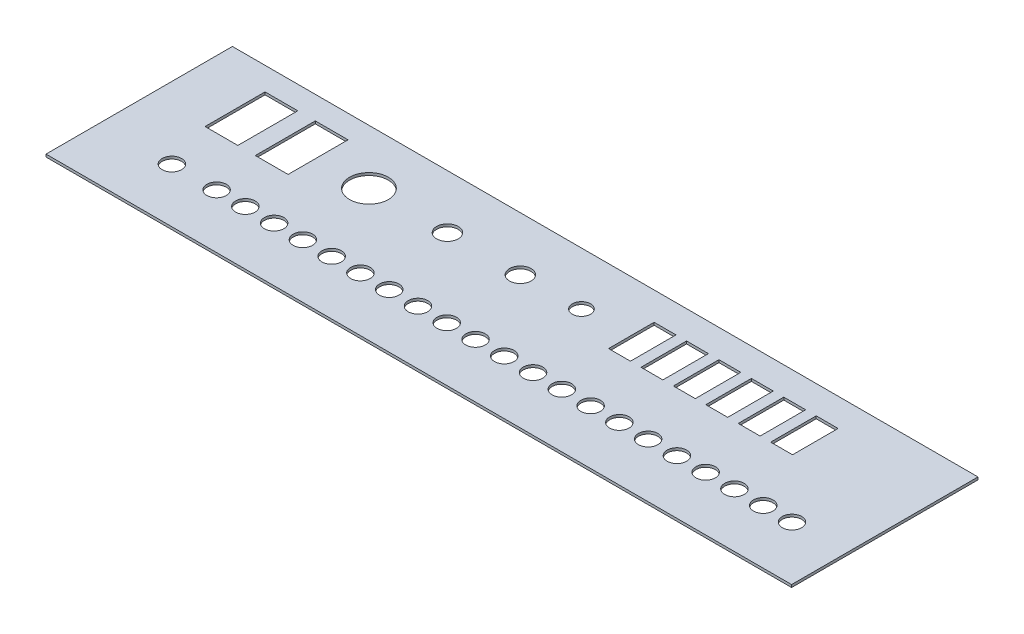
SolidWorks part; units mm, degrees
ref_plane "Front Plane" through (0, 0, 0) normal (0, 0, 1) x (1, 0, 0)
ref_plane "Top Plane" through (0, 0, 0) normal (0, 1, 0) x (1, 0, 0)
ref_plane "Right Plane" through (0, 0, 0) normal (1, 0, 0) x (0, 0, -1)
sketch "Boceto" plane through (0, 0, 0) normal (0, 1, 0) x (1, 0, 0)
  line L0 (-59.1, 30.6902) -> (-173.0029, 30.6902) construction
  line L5 (-59.1, -51.6098) -> (395.9, -51.6098) construction
  line L6 (-59.1, -51.6098) -> (-59.1, 63.3902) construction
  line L7 (-59.1, 63.3902) -> (395.9, 63.3902) construction
  line L8 (395.9, -51.6098) -> (395.9, 63.3902) construction
  line L9 (-28.6, 48.9902) -> (-8.6, 48.9902) construction
  line L10 (-28.6, 48.9902) -> (-28.6, 12.3902) construction
  line L11 (-28.6, 12.3902) -> (-8.6, 12.3902) construction
  line L12 (-8.6, 48.9902) -> (-8.6, 12.3902) construction
  line L13 (-28.6, 48.9902) -> (-8.6, 12.3902) construction
  line L14 (-28.6, 12.3902) -> (-8.6, 48.9902) construction
  line L15 (-59.1, -18.1098) -> (395.9, -18.1098) construction
  line L16 (2.4, 12.3902) -> (22.4, 12.3902) construction
  line L17 (2.4, 12.3902) -> (2.4, 48.9902) construction
  line L18 (2.4, 48.9902) -> (22.4, 48.9902) construction
  line L19 (22.4, 12.3902) -> (22.4, 48.9902) construction
  line L20 (2.4, 12.3902) -> (22.4, 48.9902) construction
  line L21 (2.4, 48.9902) -> (22.4, 12.3902) construction
  line L22 (174.9, 49.7902) -> (194.9, 49.7902) construction
  line L23 (174.9, 49.7902) -> (174.9, 11.7902) construction
  line L24 (174.9, 11.7902) -> (194.9, 11.7902) construction
  line L25 (194.9, 49.7902) -> (194.9, 11.7902) construction
  line L26 (174.9, 49.7902) -> (194.9, 11.7902) construction
  line L27 (174.9, 11.7902) -> (194.9, 49.7902) construction
  line L34 (211.4, 17.5561) -> (331, 17.5561) construction
  line L35 (211.4, 17.5561) -> (211.4, 46.5902) construction
  line L36 (211.4, 46.5902) -> (331, 46.5902) construction
  line L37 (331, 17.5561) -> (331, 46.5902) construction
  line L38 (211.4, 17.5561) -> (331, 46.5902) construction
  line L39 (211.4, 46.5902) -> (331, 17.5561) construction
  circle A0 centre (54.9, 29.6902) radius 11.1 construction
  circle A1 centre (102.75, 30.2402) radius 4.85 construction
  circle A2 centre (147.75, 30.2402) radius 4.85 construction
  circle A3 centre (-18.9, -18.1098) radius 6 construction
  circle A4 centre (8.7, -18.1098) radius 6 construction
  circle A5 centre (26.45, -18.1098) radius 6 construction
  circle A6 centre (44.2, -18.1098) radius 6 construction
  circle A7 centre (61.95, -18.1098) radius 6 construction
  circle A8 centre (79.7, -18.1098) radius 6 construction
  circle A9 centre (97.45, -18.1098) radius 6 construction
  circle A10 centre (115.2, -18.1098) radius 6 construction
  circle A11 centre (132.95, -18.1098) radius 6 construction
  circle A12 centre (150.7, -18.1098) radius 6 construction
  circle A13 centre (168.45, -18.1098) radius 6 construction
  circle A14 centre (186.2, -18.1098) radius 6 construction
  circle A15 centre (203.95, -18.1098) radius 6 construction
  circle A16 centre (221.7, -18.1098) radius 6 construction
  circle A17 centre (239.45, -18.1098) radius 6 construction
  circle A18 centre (257.2, -18.1098) radius 6 construction
  circle A19 centre (274.95, -18.1098) radius 6 construction
  circle A20 centre (292.7, -18.1098) radius 6 construction
  circle A21 centre (310.45, -18.1098) radius 6 construction
  circle A22 centre (328.2, -18.1098) radius 6 construction
  circle A23 centre (345.95, -18.1098) radius 6 construction
  circle A24 centre (363.7, -18.1098) radius 6 construction
  point P0 (0, 0)
  point P6 (-18.6, 30.6902)
  point P13 (12.4, 30.6902)
  point P24 (184.9, 30.7902)
  point P34 (271.2, 32.0731)
  point P40 (0, 0)
  point P41 (0, 0)
  dimension "D10" = 22.2
  dimension "D11" = 33.7
  dimension "D14" = 9.7
  dimension "D17" = 9.7
  dimension "D23" = 12
  dimension "D29" = 81.5
  dimension "D30" = 12
  dimension "D1" = 455
  dimension "D2" = 115
  dimension "D3" = 14.4
  dimension "D4" = 30.5
  dimension "D5" = 20
  dimension "D6" = 36.6
  dimension "D7" = 11
  dimension "D8" = 20
  dimension "D9" = 36.6
  dimension "D12" = 114
  dimension "D13" = 161.85
  dimension "D15" = 33.15
  dimension "D16" = 33.15
  dimension "D18" = 206.85
  dimension "D19" = 20
  dimension "D20" = 38
  dimension "D21" = 13.6
  dimension "D22" = 234
  dimension "D24" = 270.5
  dimension "D25" = 119.6
  dimension "D26" = 16.8
  dimension "D27" = 29.0341
  dimension "D28" = 40.2
  dimension "D31" = 27.6
  dimension "D32" = 21
sketch "Sketch4" plane through (0, 0, 0) normal (0, 1, 0) x (1, 0, 0)
  line L0 (-28.6, 48.9902) -> (-8.6, 12.3902) construction
  line L1 (-60.5474, 63.3902) -> (394.4526, 63.3902)
  line L3 (-60.5474, -51.6098) -> (394.4526, -51.6098)
  line L5 (-28.7093, 12.1902) -> (-8.4907, 12.1902)
  line L6 (-28.7093, 12.1902) -> (-28.7093, 49.1902)
  line L7 (-28.7093, 49.1902) -> (-8.4907, 49.1902)
  line L8 (-8.4907, 12.1902) -> (-8.4907, 49.1902)
  line L9 (-28.7093, 12.1902) -> (-8.4907, 49.1902) construction
  line L10 (-28.7093, 49.1902) -> (-8.4907, 12.1902) construction
  line L11 (-28.6, 12.3902) -> (-8.6, 48.9902) construction
  line L12 (2.4, 12.3902) -> (22.4, 48.9902) construction
  line L17 (2.2907, 12.1902) -> (2.2907, 49.1902)
  line L18 (2.2907, 12.1902) -> (22.5093, 12.1902)
  line L19 (22.5093, 12.1902) -> (22.5093, 49.1902)
  line L20 (2.2907, 49.1902) -> (22.5093, 49.1902)
  line L21 (102.75, 30.2402) -> (199.8359, 30.2402) construction
  line L22 (211.4, 32.0731) -> (331, 32.0731) construction
  line L23 (211.4, 17.5561) -> (211.4, 46.5902) construction
  line L24 (331, 17.5561) -> (331, 46.5902) construction
  line L25 (247.9, 46.1231) -> (247.9, 18.0231)
  line L26 (227.9, 46.1231) -> (214.4, 46.1231)
  line L27 (227.9, 46.1231) -> (227.9, 18.0231)
  line L28 (227.9, 18.0231) -> (214.4, 18.0231)
  line L29 (214.4, 46.1231) -> (214.4, 18.0231)
  line L30 (227.9, 46.1231) -> (214.4, 18.0231) construction
  line L31 (227.9, 18.0231) -> (214.4, 46.1231) construction
  line L32 (247.9, 46.1231) -> (234.4, 46.1231)
  line L33 (234.4, 46.1231) -> (234.4, 18.0231)
  line L34 (247.9, 18.0231) -> (234.4, 18.0231)
  line L35 (267.9, 46.1231) -> (267.9, 18.0231)
  line L36 (267.9, 46.1231) -> (254.4, 46.1231)
  line L37 (254.4, 46.1231) -> (254.4, 18.0231)
  line L38 (267.9, 18.0231) -> (254.4, 18.0231)
  line L39 (287.9, 46.1231) -> (287.9, 18.0231)
  line L40 (287.9, 46.1231) -> (274.4, 46.1231)
  line L41 (274.4, 46.1231) -> (274.4, 18.0231)
  line L42 (287.9, 18.0231) -> (274.4, 18.0231)
  line L43 (307.9, 46.1231) -> (307.9, 18.0231)
  line L44 (307.9, 46.1231) -> (294.4, 46.1231)
  line L45 (294.4, 46.1231) -> (294.4, 18.0231)
  line L46 (307.9, 18.0231) -> (294.4, 18.0231)
  line L47 (327.9, 46.1231) -> (327.9, 18.0231)
  line L48 (327.9, 46.1231) -> (314.4, 46.1231)
  line L49 (314.4, 46.1231) -> (314.4, 18.0231)
  line L50 (327.9, 18.0231) -> (314.4, 18.0231)
  line L52 (-60.5474, 63.3902) -> (-63.0474, 63.3902)
  line L54 (-60.5474, -51.6098) -> (-63.0474, -51.6098)
  line L55 (-63.0474, 63.3902) -> (-63.0474, -51.6098)
  line L56 (394.4526, -51.6098) -> (396.9526, -51.6098)
  line L58 (394.4526, 63.3902) -> (396.9526, 63.3902)
  line L59 (396.9526, -51.6098) -> (396.9526, 63.3902)
  circle A0 centre (54.9, 29.6902) radius 11.95
  circle A1 centre (102.75, 30.2402) radius 6.65
  circle A4 centre (147.75, 30.2402) radius 6.65
  circle A6 centre (184.9, 30.7902) radius 5.6
  circle A7 centre (-18.9, -18.1098) radius 6
  circle A8 centre (8.7, -18.1098) radius 6
  circle A9 centre (26.45, -18.1098) radius 6
  circle A10 centre (44.2, -18.1098) radius 6
  circle A11 centre (61.95, -18.1098) radius 6
  circle A12 centre (79.7, -18.1098) radius 6
  circle A13 centre (97.45, -18.1098) radius 6
  circle A14 centre (115.2, -18.1098) radius 6
  circle A15 centre (132.95, -18.1098) radius 6
  circle A16 centre (150.7, -18.1098) radius 6
  circle A17 centre (168.45, -18.1098) radius 6
  circle A18 centre (186.2, -18.1098) radius 6
  circle A19 centre (203.95, -18.1098) radius 6
  circle A20 centre (221.7, -18.1098) radius 6
  circle A21 centre (239.45, -18.1098) radius 6
  circle A22 centre (257.2, -18.1098) radius 6
  circle A23 centre (274.95, -18.1098) radius 6
  circle A24 centre (292.7, -18.1098) radius 6
  circle A25 centre (310.45, -18.1098) radius 6
  circle A26 centre (328.2, -18.1098) radius 6
  circle A27 centre (345.95, -18.1098) radius 6
  circle A28 centre (363.7, -18.1098) radius 6
  point P6 (-18.6, 30.6902)
  point P15 (12.4, 30.6902)
  point P40 (221.15, 32.0731)
  dimension "D3" = 23.9
  dimension "D4" = 13.3
  dimension "D5" = 2
  dimension "D6" = 11.2
  dimension "D11" = 12
  dimension "D1" = 37
  dimension "D2" = 2
  dimension "D7" = 13.5
  dimension "D8" = 28.1
  dimension "D9" = 3
  dimension "D14" = 2.5
  dimension "D15" = 2.5
  dimension "D10" = 6
  dimension "D12" = 21
extrude "Boss-Extrude1" add sketch "Sketch4" along normal blind 1.6
